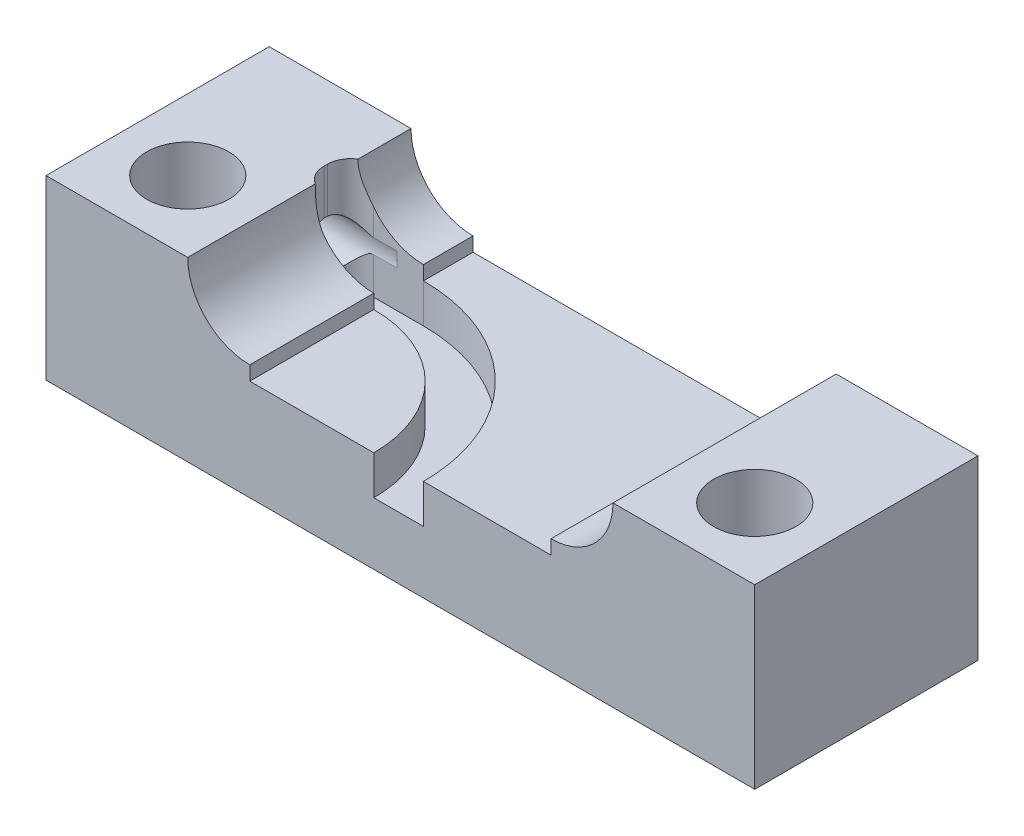
SolidWorks part; units mm, degrees
ref_plane "Front Plane" through (0, 0, 0) normal (0, 0, 1) x (1, 0, 0)
ref_plane "Top Plane" through (0, 0, 0) normal (0, 1, 0) x (1, 0, 0)
ref_plane "Right Plane" through (0, 0, 0) normal (1, 0, 0) x (0, 0, -1)
sketch "Sketch1" plane through (0, 0, 0) normal (0, 1, 0) x (1, 0, 0)
  line L1 (-12.7, -4.0005) -> (12.7, -4.0005)
  line L2 (-12.7, -4.0005) -> (-12.7, 4.0005)
  line L3 (-12.7, 4.0005) -> (12.7, 4.0005)
  line L4 (12.7, -4.0005) -> (12.7, 4.0005)
  line L5 (-12.7, -4.0005) -> (12.7, 4.0005) construction
  line L6 (-12.7, 4.0005) -> (12.7, -4.0005) construction
  point P0 (0, 0)
  dimension "D1" = 25.4
  dimension "D2" = 8.001
extrude "Boss-Extrude1" add sketch "Sketch1" along normal blind 6.35
sketch "Sketch2" plane through (0, 0, -4.0005) normal (0, 0, -1) x (-1, 0, 0)
  line L0 (5.3975, 6.35) -> (-5.3975, 6.35) construction
  line L1 (5.3975, 4.1275) -> (-5.3975, 4.1275)
  line L2 (5.3975, 8.5725) -> (-5.3975, 8.5725)
  line L3 (12.7, 6.35) -> (-12.7, 6.35) construction
  line L4 (-12.7, 0) -> (12.7, 0) construction
  line L6 (12.7, 6.35) -> (12.7, 0) construction
  line L7 (-12.7, 6.35) -> (-12.7, 0) construction
  arc A0 (5.3975, 4.1275) -> (5.3975, 8.5725) centre (5.3975, 6.35) ccw
  arc A1 (-5.3975, 8.5725) -> (-5.3975, 4.1275) centre (-5.3975, 6.35) ccw
  point P2 (0, 6.35)
  dimension "D1" = 6.35
  dimension "D2" = 10.795
  dimension "D3" = 4.445
extrude "Cut-Extrude1" cut sketch "Sketch2" against normal blind 25.4
ref_plane "Plane1" through (0, 4.1275, 0) normal (0, 1, 0) x (1, 0, 0)
sketch "Sketch4" plane through (0, 4.1275, 0) normal (0, 1, 0) x (1, 0, 0)
  line L1 (0.8255, -4.0005) -> (-0.9525, -4.0005)
  line L2 (-5.3975, 0.4445) -> (-7.1855, 0.4445)
  line L3 (-8.011, 1.27) -> (-8.011, 1.397)
  line L4 (-7.1855, 2.2225) -> (-5.3975, 2.2225)
  arc A0 (-0.9525, -4.0005) -> (-5.3975, 0.4445) centre (-5.3975, -4.0005) ccw
  arc A1 (0.8255, -4.0005) -> (-5.3975, 2.2225) centre (-5.3975, -4.0005) ccw
  arc A2 (-8.011, 1.27) -> (-7.1855, 0.4445) centre (-7.1855, 1.27) ccw
  arc A3 (-7.1855, 2.2225) -> (-8.011, 1.397) centre (-7.1855, 1.397) ccw
  dimension "D1" = 8.89
  dimension "D2" = 12.446
  dimension "D3" = 2.6135
  dimension "D4" = 1.778
  dimension "D5" = 0.8255
extrude "Cut-Extrude2" cut sketch "Sketch4" against normal blind 1.905 and the other way through all
ref_plane "Plane3" through (-12.7, 0, 0) normal (-1, 0, 0) x (0, 0, 1)
sketch "Sketch5" plane through (12.7, 0, 0) normal (1, 0, 0) x (0, 0, -1)
  line L0 (-4.0005, 6.35) -> (-4.0005, 0) construction
  line L1 (-4.0005, 6.35) -> (4.0005, 6.35) construction
  circle A0 centre (1.3335, 3.81) radius 0.9271
  dimension "D2" = 1.8542
  dimension "D1" = 5.334
  dimension "D3" = 2.54
extrude "Cut-Extrude3" cut sketch "Sketch5" along normal blind 6.35 from surface starting at plane "Plane3"
fillet "Fillet3" [suppressed] radius 6.35
sketch "Sketch6" plane through (0, 4.1275, 0) normal (0, 1, 0) x (1, 0, 0)
  line L1 (5.3975, -4.0005) -> (-5.3975, -4.0005)
  line L2 (5.3975, -4.0005) -> (5.3975, 4.0005)
  line L3 (5.3975, 4.0005) -> (-5.3975, 4.0005)
  line L4 (-5.3975, -4.0005) -> (-5.3975, 4.0005)
extrude "Cut-Extrude4" cut sketch "Sketch6" against normal blind 0.508
hole_wizard "#4 Clearance Hole1" positions "Sketch8" profile "Sketch7" hole size "#4" standard "ANSI Inch" end condition through all
sketch "Sketch8" plane through (0, 0, 0) normal (0, -1, 0) x (-1, 0, 0)
  line L0 (12.7, -4.0005) -> (-12.7, -4.0005) construction
  line L1 (-12.7, -4.0005) -> (-12.7, 4.0005) construction
  line L2 (12.7, 4.0005) -> (12.7, -4.0005) construction
  point P0 (-10.16, -1.4605)
  point P2 (10.16, -1.4605)
  dimension "D1" = 2.54
  dimension "D2" = 2.54
  dimension "D3" = 2.54
sketch "Sketch7" plane through (10.16, 0, 1.4605) normal (1, 0, 0) x (0, 0, -1)
  line L0 (0, 0) -> (0, 6.35)
  line L1 (0, 6.35) -> (1.4732, 6.35)
  line L2 (1.4732, 6.35) -> (1.4732, 0.635)
  line L3 (1.4732, 0.635) -> (2.1082, 0)
  line L5 (2.1082, 0) -> (0, 0)
  line L6 (-1.4732, 0.635) -> (-2.1082, 0) construction
  line L11 (0, -6.35) -> (0, 107.95) construction
  dimension "Thru Hole Dia." = 2.9464
  dimension "Thru Hole Depth" = 6.35
  dimension "Near C'Sink Dia." = 4.2164
  dimension "Near C'Sink Angle" = 90
